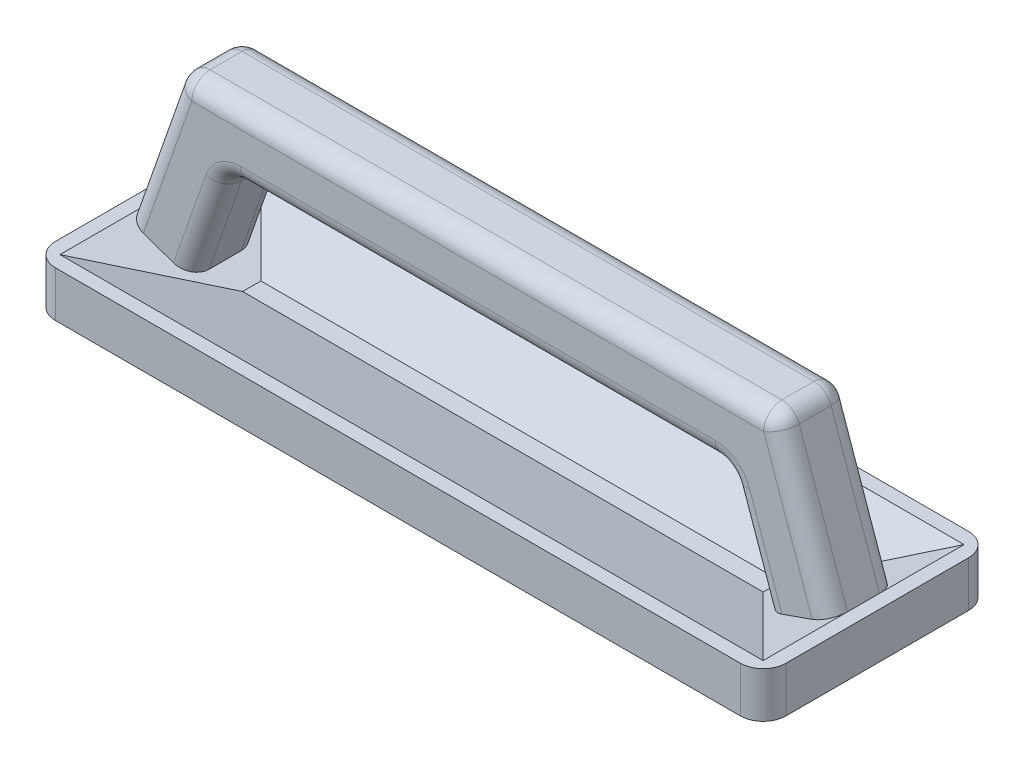
SolidWorks part; units mm, degrees
ref_plane "Front Plane" through (0, 0, 0) normal (0, 0, 1) x (1, 0, 0)
ref_plane "Top Plane" through (0, 0, 0) normal (0, 1, 0) x (1, 0, 0)
ref_plane "Right Plane" through (0, 0, 0) normal (1, 0, 0) x (0, 0, -1)
sketch "Sketch1" plane through (0, 0, 0) normal (0, 1, 0) x (1, 0, 0)
  line L1 (-80, -25) -> (80, -25)
  line L2 (-80, -25) -> (-80, 25)
  line L3 (-80, 25) -> (80, 25)
  line L4 (80, -25) -> (80, 25)
  line L5 (-80, -25) -> (80, 25) construction
  line L6 (-80, 25) -> (80, -25) construction
  point P0 (0, 0)
  dimension "D1" = 160
  dimension "D2" = 50
extrude "Boss-Extrude1" add sketch "Sketch1" along normal blind 10
shell "Shell3" thickness 3 removed face at (0, 10, 0)
fillet "Fillet1" radius 5 4 edges at (80, 5, -25) (80, 5, 25) (-80, 5, 25) (-80, 5, -25)
chamfer "Chamfer1" distance 7 distance2 20 4 edges at (0, 3, 22) (-77, 3, 0) (0, 3, -22) (77, 3, 0) first distance on face at (0, 6.5, 22) first distance on face at (-77, 6.5, 0) first distance on face at (0, 6.5, -22) first distance on face at (77, 6.5, 0)
sketch "Sketch2" plane through (0, 0, 0) normal (0, 0, 1) x (1, 0, 0)
  line L0 (-77, 10) -> (-57, 3)
  line L1 (-77, 10) -> (-57, 3)
  line L2 (-57, 3) -> (57, 3)
  line L3 (-57, 3) -> (57, 3)
  line L4 (57, 3) -> (77, 10)
  line L5 (57, 3) -> (77, 10)
  line L6 (-77, 10) -> (-65.45, 43)
  line L7 (-65.45, 43) -> (65.45, 43)
  line L8 (65.45, 43) -> (77, 10)
  line L9 (-62.8421, 5.0447) -> (-54.8078, 28)
  line L10 (-54.8078, 28) -> (54.8078, 28)
  line L11 (54.8078, 28) -> (62.8421, 5.0447)
  point P13 (0, 28)
  dimension "D1" = 15
  dimension "D2" = 15
  dimension "D3" = 15
  dimension "D4" = 25
  dimension "D5" = 90
extrude "Boss-Extrude2" add sketch "Sketch2" along normal blind 7.5 and the other way blind 7.5 contours L10 L11 L5 L8 L7 L6 L1 L9 region at (0, 31.1277, 0)
fillet "Fillet2" radius 4 16 edges at (-54.8078, 28, 0) (54.8078, 28, 0) (65.45, 43, 0) (-65.45, 43, 0) (71.225, 26.5, 7.5) (0, 43, 7.5) (58.825, 16.5224, 7.5) (0, 28, 7.5) (-58.825, 16.5224, 7.5) (-71.225, 26.5, 7.5) (-58.825, 16.5224, -7.5) (0, 28, -7.5) (58.825, 16.5224, -7.5) (71.225, 26.5, -7.5) (0, 43, -7.5) (-71.225, 26.5, -7.5)
